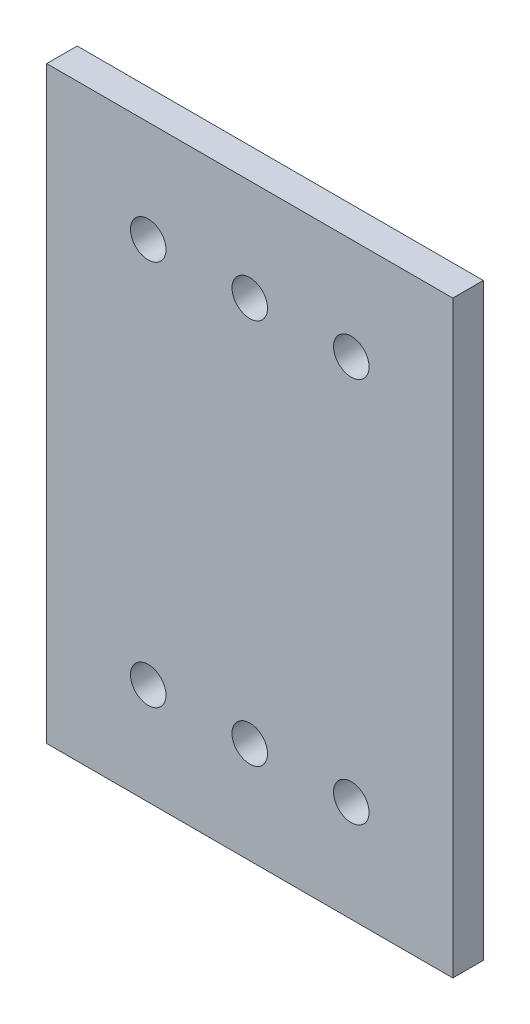
SolidWorks part; units mm, degrees
ref_plane "Front Plane" through (0, 0, 0) normal (0, 0, 1) x (1, 0, 0)
ref_plane "Top Plane" through (0, 0, 0) normal (0, 1, 0) x (1, 0, 0)
ref_plane "Right Plane" through (0, 0, 0) normal (1, 0, 0) x (0, 0, -1)
sketch "Sketch1" plane through (0, 0, 0) normal (0, 0, 1) x (1, 0, 0)
  line L1 (0, 0) -> (40, 0)
  line L2 (0, 0) -> (0, 58)
  line L3 (0, 58) -> (40, 58)
  line L4 (40, 0) -> (40, 58)
  circle A0 centre (10, 10) radius 1.75
  circle A1 centre (20, 10) radius 1.75
  circle A2 centre (30, 10) radius 1.75
  circle A3 centre (10, 48) radius 1.75
  circle A4 centre (20, 48) radius 1.75
  circle A5 centre (30, 48) radius 1.75
  dimension "D2" = 3.5
  dimension "D3" = 10
  dimension "D4" = 10
  dimension "D6" = 10
  dimension "D8" = 10
  dimension "D9" = 3.5
  dimension "D10" = 38
  dimension "D12" = 10
  dimension "D1" = 40
  dimension "D7" = 10
  dimension "D5" = 3
  dimension "D11" = 3
extrude "Boss-Extrude1" add sketch "Sketch1" along normal blind 3
